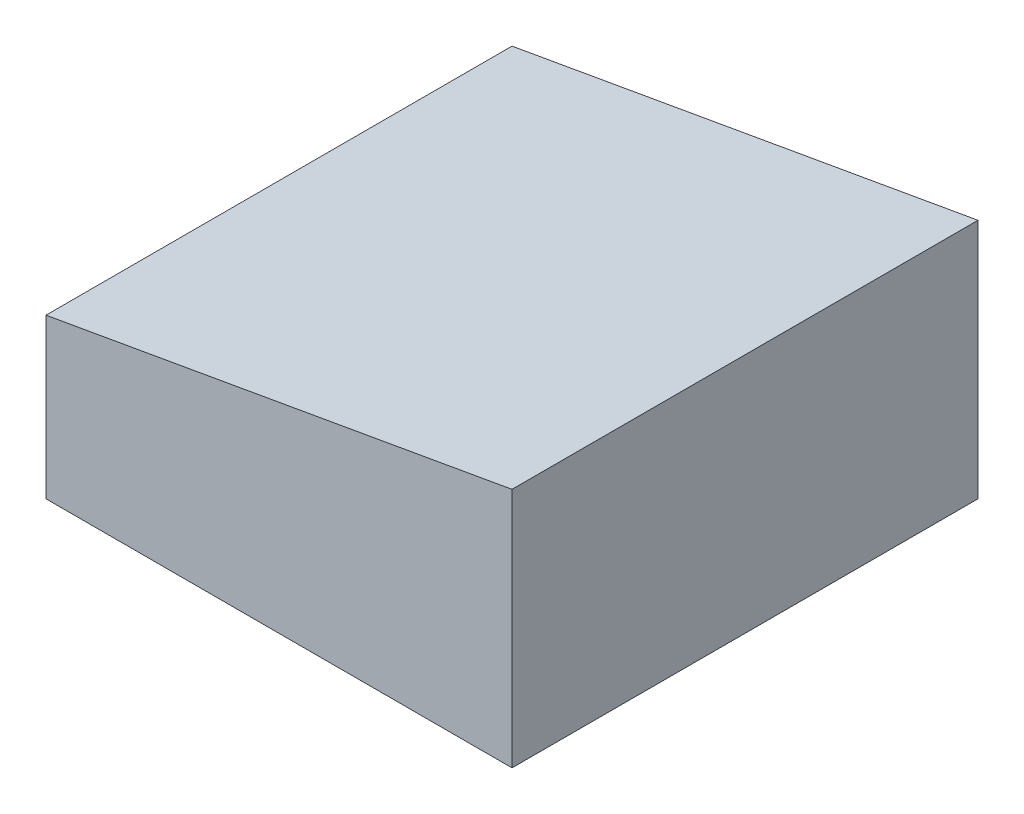
SolidWorks part; units mm, degrees
ref_plane "Front Plane" through (0, 0, 0) normal (0, 0, 1) x (1, 0, 0)
ref_plane "Top Plane" through (0, 0, 0) normal (0, 1, 0) x (1, 0, 0)
ref_plane "Right Plane" through (0, 0, 0) normal (1, 0, 0) x (0, 0, -1)
sketch "Sketch1" plane through (0, 0, 0) normal (0, 0, 1) x (1, 0, 0)
  line L0 (50.8, 26.2976) -> (0, 17.3402)
  line L1 (0, 0) -> (50.8, 0)
  line L2 (0, 0) -> (0, 17.3402)
  line L4 (50.8, 0) -> (50.8, 26.2976)
  dimension "D1" = 50.8
  dimension "D2" = 80
  dimension "D3" = 17.3402
extrude "Boss-Extrude1" add sketch "Sketch1" along normal blind 50.8
